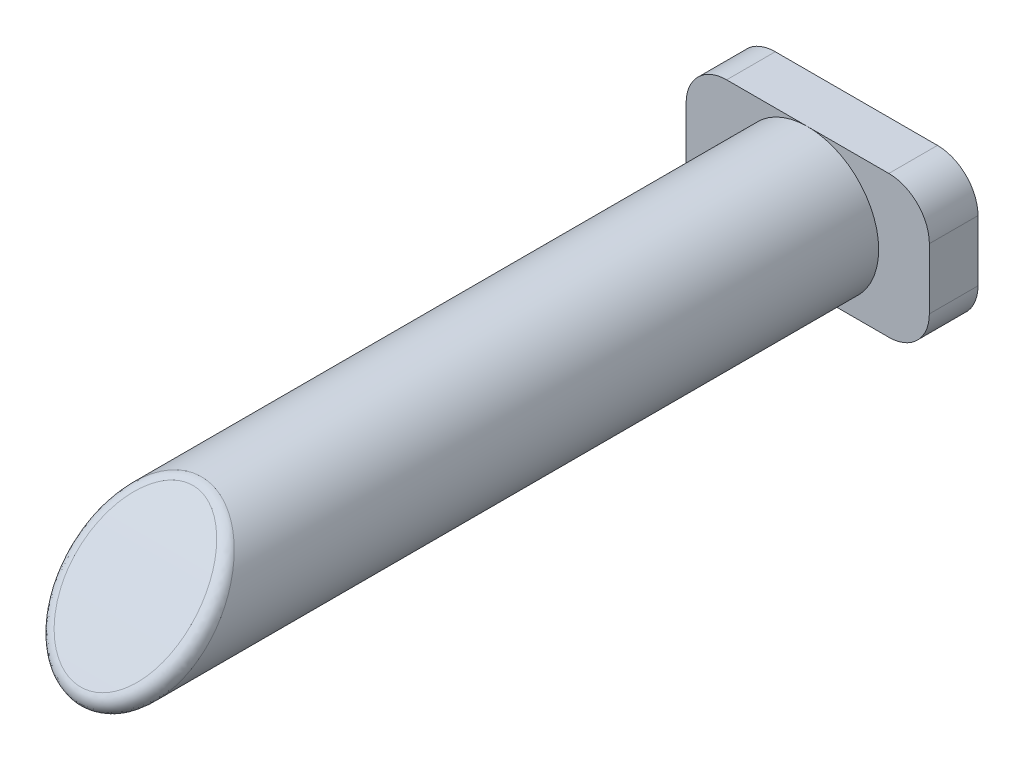
SolidWorks part; units mm, degrees
ref_plane "Plan de face" through (0, 0, 0) normal (0, 0, 1) x (1, 0, 0)
ref_plane "Plan de dessus" through (0, 0, 0) normal (0, 1, 0) x (1, 0, 0)
ref_plane "Plan de droite" through (0, 0, 0) normal (1, 0, 0) x (0, 0, -1)
sketch "Esquisse1" plane through (0, 0, 0) normal (0, 0, 1) x (1, 0, 0)
  line L1 (-6, 3.5) -> (0, 3.5)
  line L2 (-6, 3.5) -> (-6, 0)
  line L3 (-6, 0) -> (0, 0)
  line L4 (0, 3.5) -> (0, 0)
  dimension "D1" = 3.5
  dimension "D2" = 6
extrude "Boss.-Extru.1" add sketch "Esquisse1" along normal blind 1.2
sketch "Esquisse2" plane through (0, 0, 1.2) normal (0, 0, 1) x (1, 0, 0)
  line L0 (0, 0) -> (0, 3.5) construction
  line L1 (0, 3.5) -> (-6, 3.5) construction
  circle A0 centre (-3, 1.75) radius 1.75
  dimension "D1" = 3
  dimension "D3" = 3.5
  dimension "D2" = 1.75
extrude "Boss.-Extru.2" add sketch "Esquisse2" along normal blind 18.5
sketch "Esquisse4" plane through (0, 0, 0) normal (1, 0, 0) x (0, 0, -1)
  line L1 (-1.2, 3.5) -> (-1.2, 0) construction
  line L2 (4.0315, 14.1321) -> (2.3617, 22.1931)
  line L3 (-29.2446, -26.0804) -> (-28.8039, 1.396)
  arc A0 (4.0315, 14.1321) -> (-29.2446, -26.0804) centre (12.5, -26.75) ccw
  arc A1 (2.3617, 22.1931) -> (-28.8039, 1.396) centre (12.5, -26.75) ccw
  point P4 (-1.2, 1.75)
  dimension "D1" = 83.5
  dimension "D2" = 28.5
extrude "Enlèv. mat.-Extru.1" cut sketch "Esquisse4" against normal blind 10
fillet "Congé1" radius 0.3 1 edges at (-1.2865, 1.3946, 18.3373)
fillet "Congé2" radius 1 4 edges at (-6, 3.5, 0.6) (0, 3.5, 0.6) (-6, 0, 0.6) (0, 0, 0.6)
